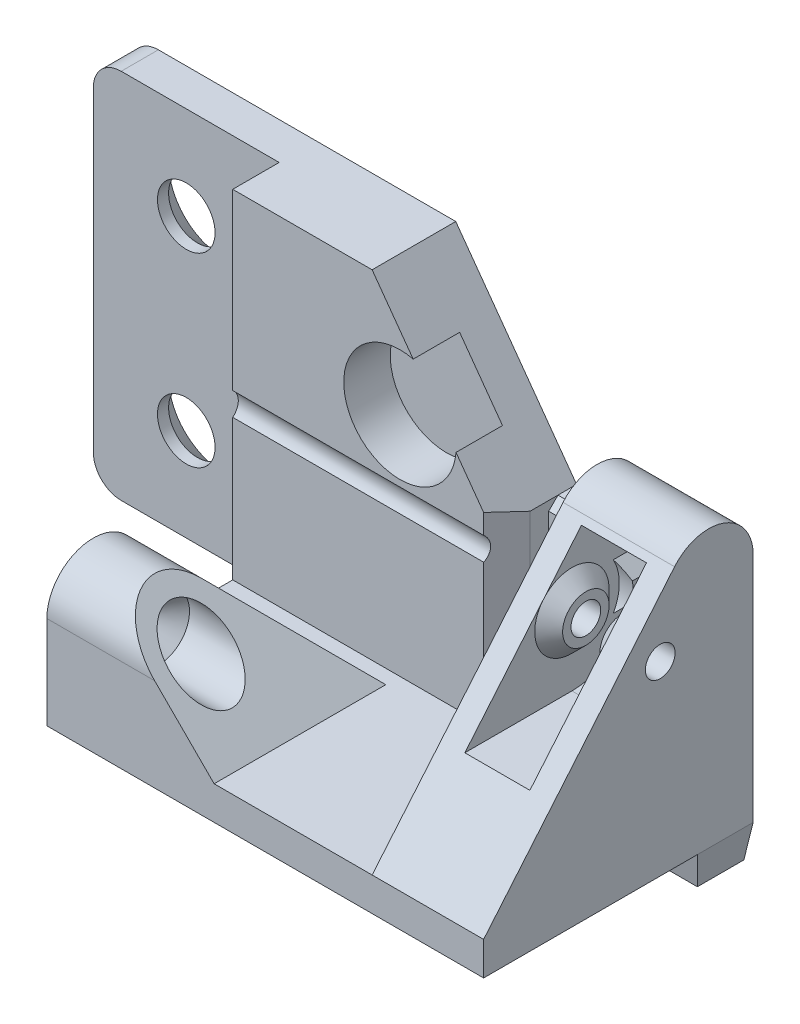
SolidWorks part; units mm, degrees
ref_plane "Front Plane" through (0, 0, 0) normal (0, 0, 1) x (1, 0, 0)
ref_plane "Top Plane" through (0, 0, 0) normal (0, 1, 0) x (1, 0, 0)
ref_plane "Right Plane" through (0, 0, 0) normal (1, 0, 0) x (0, 0, -1)
sketch "Sketch1" plane through (0, 0, 0) normal (0, 0, 1) x (1, 0, 0)
  line L0 (-10, -20) -> (-10, 0) construction
  line L1 (-10, -20) -> (10, -20) construction
  line L2 (-10, 0) -> (10, 0) construction
  line L3 (10, -20) -> (10, 0) construction
  line L4 (-10, -20) -> (10, 0) construction
  line L5 (-10, 0) -> (10, -20) construction
  line L6 (-10, 0) -> (-10, 20) construction
  line L7 (-10, 17) -> (-10, -17)
  line L8 (-10, 20) -> (10, 20) construction
  line L9 (10, 0) -> (10, 20) construction
  line L10 (-10, 0) -> (10, 20) construction
  line L11 (-10, 20) -> (10, 0) construction
  line L12 (-7, 20) -> (10, 20)
  line L13 (57, 20) -> (57, -20)
  line L14 (45, 20) -> (57, 20)
  line L15 (10, 20) -> (25, 20)
  line L16 (25, 20) -> (38, 2)
  line L17 (45, 20) -> (45, 2)
  line L18 (57, -20) -> (-7, -20)
  line L20 (45, 2) -> (38, 2)
  circle A0 centre (0, 10) radius 3.1
  circle A1 centre (0, -10) radius 3.1
  arc A2 (-7, 20) -> (-10, 17) centre (-7, 17) ccw
  arc A3 (-10, -17) -> (-7, -20) centre (-7, -17) ccw
  point P0 (0, 10)
  point P1 (0, -10)
  dimension "D2" = 6.2
  dimension "D6" = 3
  dimension "D1" = 20
  dimension "D3" = 57
  dimension "D4" = 12
  dimension "D5" = 15
  dimension "D8" = 18
  dimension "D9" = 7
extrude "Boss-Extrude1" add sketch "Sketch1" along normal blind 9
sketch "Sketch2" plane through (0, 0, 9) normal (0, 0, 1) x (1, 0, 0)
  line L0 (25, 20) -> (-7, 20) construction
  line L1 (10, 20) -> (-10, 20)
  line L2 (10, 20) -> (10, -20)
  line L3 (10, -20) -> (-10, -20)
  line L4 (-10, 20) -> (-10, -20)
  line L5 (-10, 20) -> (10, -20) construction
  line L6 (10, 20) -> (-10, -20) construction
  line L7 (-10, 17) -> (-10, -17) construction
  point P6 (0, 0)
extrude "Cut-Extrude1" cut sketch "Sketch2" against normal offset from surface (5 mm away) 4 up to face at (3.1, 10, 0)
sketch "Sketch3" plane through (0, 0, 9) normal (0, 0, 1) x (1, 0, 0)
  line L0 (10, 20) -> (10, -20) construction
  circle A0 centre (28, 8) radius 6.05
  dimension "D2" = 8
  dimension "D3" = 12.1
  dimension "D1" = 18
extrude "Cut-Extrude2" cut sketch "Sketch3" against normal up to surface (5 mm away) up to face at (3.1, 10, 4)
sketch "Sketch4" plane through (0, 0, 9) normal (0, 0, 1) x (1, 0, 0)
  line L0 (57, -20) -> (57, 20)
  line L1 (57, 20) -> (45, 20)
  line L2 (45, 20) -> (45, -16.4)
  line L3 (45, -16.4) -> (10, -16.4)
  line L4 (10, 20) -> (10, -20) construction
  line L5 (10, -16.4) -> (10, -20)
  line L6 (10, -20) -> (57, -20)
  dimension "D1" = 3.6
extrude "Boss-Extrude2" add sketch "Sketch4" along normal blind 20
sketch "Sketch6" plane through (57, 0, 0) normal (1, 0, 0) x (0, 0, -1)
  line L2 (-8.4527, 8.0537) -> (-29, -16.4)
  line L10 (-29, 20) -> (-29, -16.4)
  line L14 (-29, 20) -> (0, 20)
  line L15 (0, 20) -> (0, 4.9739)
  line L16 (0, -20) -> (0, 20) construction
  circle A0 centre (-10, 0) radius 1.6
  circle A1 centre (-10, 0) radius 5.5 construction
  arc A3 (-8.4527, 8.0537) -> (0, 4.9739) centre (-4.7874, 4.9739) cw
  dimension "D3" = 10
extrude "Cut-Extrude4" cut sketch "Sketch6" against normal up to next
ref_plane "Plane1" through (51, 0, 0) normal (1, 0, 0) x (0, 0, -1)
sketch "Sketch5" plane through (51, 0, 0) normal (1, 0, 0) x (0, 0, -1)
  line L1 (-29, -20) -> (-29, -16.4) construction
  line L2 (-10, 7.5) -> (-29, 7.5)
  line L3 (-29, 7.5) -> (-29, -7.5)
  line L4 (-29, -7.5) -> (-10, -7.5)
  arc A0 (-10, -7.5) -> (-10, 7.5) centre (-10, 0) ccw
  circle A2 centre (-10, 0) radius 1.6 construction
  dimension "D3" = 15
extrude "Cut-Extrude3" cut sketch "Sketch5" against normal blind 3.5 and the other way blind 3.5
sketch "Sketch7" plane through (0, 0, 0) normal (0, 0, -1) x (-1, 0, 0)
  line L0 (-51, 15.95) -> (-51, -15.95) construction
  line L1 (7, -20) -> (-57, -20) construction
  circle A0 centre (-51, -8) radius 1.6
  dimension "D1" = 3.2
  dimension "D2" = 12
extrude "Cut-Extrude5" [suppressed] cut sketch "Sketch7" against normal through all
sketch "Sketch8" [suppressed] plane through (0, 0, 29) normal (0, 0, 1) x (1, 0, 0)
  line L0 (54.5, -5.0065) -> (47.5, -5.0065)
  line L1 (54.1754, -8) -> (54.5, -8.5622)
  line L3 (47.5, -8.5622) -> (47.8246, -8)
  line L4 (47.8246, -8) -> (49.4123, -10.75)
  line L5 (49.4123, -10.75) -> (52.5877, -10.75)
  line L6 (52.5877, -10.75) -> (54.1754, -8)
  line L7 (47.5, -5.0065) -> (47.5, -8.5622)
  line L8 (54.5, -5.0065) -> (54.5, -8.5622)
  line L10 (49, -5.25) -> (47.4123, -5.25) [skipped]
  circle A0 centre (51, -8) radius 2.75 construction
  circle A1 centre (51, -8) radius 1.6 construction
  dimension "D1" = 5.5
extrude "Cut-Extrude6" [suppressed] cut sketch "Sketch8" against normal blind 2
chamfer "Chamfer1" [suppressed] distance 2 angle 45
sketch "Sketch9" [suppressed] plane through (0, 0, 0) normal (0, 0, -1) x (-1, 0, 0)
  circle A0 centre (-51, -8) radius 3.35
  circle A1 centre (-51, -8) radius 1.6 construction
  dimension "D1" = 6.7
extrude "Cut-Extrude7" [suppressed] cut sketch "Sketch9" against normal offset from surface (12 mm away) 15 up to face at (3.1, -10, 0)
chamfer "Chamfer2" [suppressed] distance 1.8 angle 45
sketch "Sketch11" plane through (0, 0, 9) normal (0, 0, 1) x (1, 0, 0)
  line L1 (45, 2) -> (38, 2)
  line L2 (45, 2) -> (45, -10)
  line L3 (45, -10) -> (38, -10)
  line L4 (38, 2) -> (38, -10)
  dimension "D1" = 12
extrude "Cut-Extrude9" cut sketch "Sketch11" against normal offset from surface (6 mm away) 3 up to face at (3.1, -10, 0)
chamfer "Chamfer3" distance 6 distance2 4 1 edges at (41.5, -10, 9) first distance on face at (33.9167, -9.9456, 9)
chamfer "Chamfer4" distance 1 angle 45 1 edges at (41.5, 2, 3)
sketch "Sketch12" plane through (47.5, 0, 0) normal (1, 0, 0) x (0, 0, -1)
  line L0 (-5.5548, 2.5) -> (-2.8222, 2.5)
  line L1 (-5.5548, -2.5) -> (-2.8222, -2.5)
  circle A0 centre (-10, 0) radius 2.5
  circle A1 centre (-10, 0) radius 1.6
  circle A2 centre (-10, 0) radius 1.6 construction
  arc A3 (-2.8222, -2.5) -> (-2.8222, 2.5) centre (-10, 0) ccw
  arc A5 (-5.5548, -2.5) -> (-5.5548, 2.5) centre (-10, 0) ccw
  dimension "D1" = 5
  dimension "D2" = 10.2
extrude "Boss-Extrude3" add sketch "Sketch12" along normal blind 1.5
sketch "Sketch13" plane through (54.5, 0, 0) normal (-1, 0, 0) x (0, 0, 1)
  line L0 (5.5548, 2.5) -> (2.9289, 2.5)
  line L1 (5.5548, -2.5) -> (2.9289, -2.5)
  circle A0 centre (10, 0) radius 1.6
  circle A1 centre (10, 0) radius 2.5
  arc A2 (5.5548, 2.5) -> (5.5548, -2.5) centre (10, 0) ccw
  arc A3 (2.9289, 2.5) -> (2.9289, -2.5) centre (10, 0) ccw
  circle A4 centre (10, 0) radius 2.5 construction
  circle A5 centre (10, 0) radius 1.6 construction
extrude "Boss-Extrude4" add sketch "Sketch13" along normal blind 1.5
chamfer "Chamfer6" distance 1.5 angle 45 6 edges at (54.5, 2.5, 10) (47.5, 2.5, 10) (49, -2.5, 4.2419) (49, 2.5, 4.2419) (53, -2.5, 4.2419) (53, 2.5, 4.2419)
sketch "Sketch14" plane through (0, -20, 0) normal (0, -1, 0) x (1, 0, 0)
  line L1 (57, 0) -> (51, 0)
  line L2 (57, 0) -> (57, 6)
  line L3 (57, 6) -> (51, 6)
  line L4 (51, 0) -> (51, 6)
  dimension "D1" = 6
extrude "Boss-Extrude5" add sketch "Sketch14" along normal blind 4
chamfer "Chamfer7" distance 4 distance2 1 3 edges at (54, -24, 6) (51, -24, 3) (57, -24, 3) first distance on face at (54, -22, 6) first distance on face at (51, -22, 3) first distance on face at (57, 1.6, 10)
chamfer "Chamfer8" distance 1 distance2 4 1 edges at (38, -8.6245, 9) first distance on face at (33.9167, -12.4456, 9)
chamfer "Chamfer9" distance 2.8 angle 45 2 edges at (3.1, -10, 0) (3.1, 10, 0)
sketch "Sketch15" plane through (10, 0, 0) normal (-1, 0, 0) x (0, 0, 1)
  line L0 (29, -10) -> (29, -16.4)
  line L1 (29, -16.4) -> (10.5289, -16.4)
  line L2 (29, -16.4) -> (9, -16.4) construction
  line L3 (10.5289, -16.4) -> (20.4645, -6.4645)
  line L4 (4, -20) -> (29, -20) construction
  arc A0 (29, -10) -> (20.4645, -6.4645) centre (24, -10) ccw
  dimension "D1" = 5
  dimension "D2" = 45
  dimension "D3" = 10
extrude "Boss-Extrude6" add sketch "Sketch15" against normal blind 6
chamfer "Chamfer10" distance 12 angle 45 1 edges at (16, -16.4, 19.7645)
sketch "Sketch16" plane through (10, 0, 0) normal (-1, 0, 0) x (0, 0, 1)
  circle A0 centre (24, -10) radius 1.55
  arc A1 (29, -10) -> (20.4645, -6.4645) centre (24, -10) ccw construction
  dimension "D1" = 3.1
extrude "Cut-Extrude10" cut sketch "Sketch16" against normal up to next
sketch "Sketch17" plane through (10, 0, 0) normal (-1, 0, 0) x (0, 0, 1)
  circle A0 centre (24, -10) radius 3.35
  circle A1 centre (24, -10) radius 1.55 construction
  dimension "D1" = 6.7
extrude "Cut-Extrude11" cut sketch "Sketch17" against normal up to next from offset 7 offset against normal yes
chamfer "Chamfer11" distance 1.8 angle 45 1 edges at (17, -11.55, 24)
